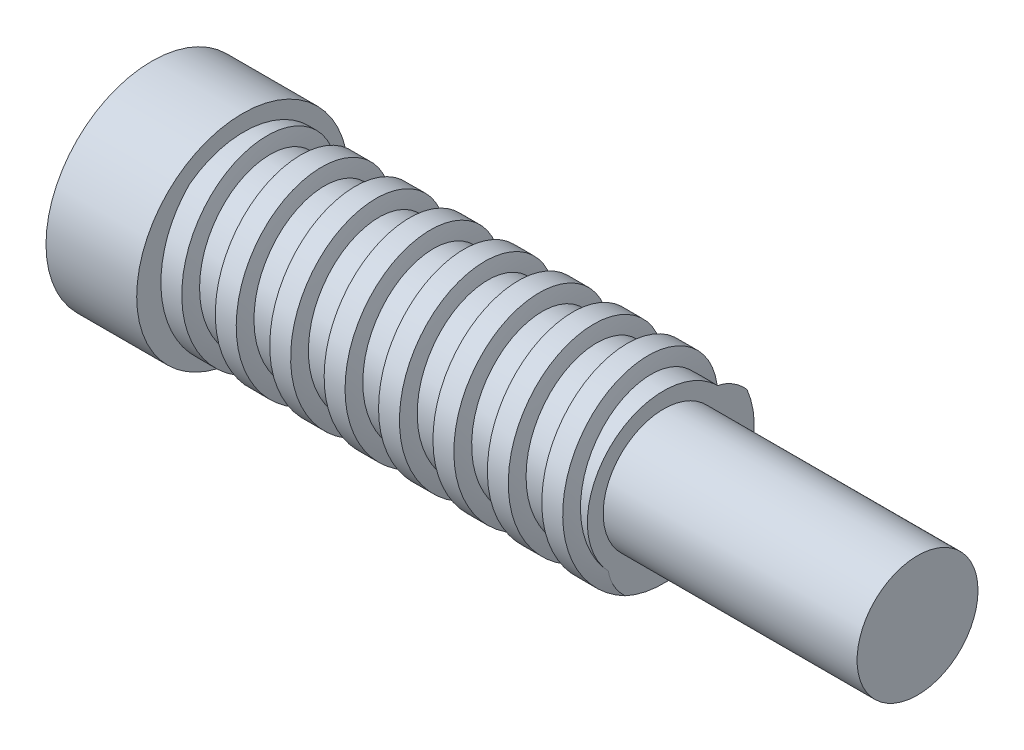
SolidWorks part; units mm, degrees
ref_plane "Piano frontale" through (0, 0, 0) normal (0, 0, 1) x (1, 0, 0)
ref_plane "Piano superiore" through (0, 0, 0) normal (0, 1, 0) x (1, 0, 0)
ref_plane "Piano destro" through (0, 0, 0) normal (1, 0, 0) x (0, 0, -1)
sketch "Schizzo1" plane through (0, 0, 0) normal (0, 0, 1) x (1, 0, 0)
  line L1 (3.0478, 1.2286) -> (21.0478, 1.2286)
  line L2 (3.0478, 1.2286) -> (3.0478, 4.2286)
  line L3 (3.0478, 4.2286) -> (21.0478, 4.2286)
  line L4 (21.0478, 1.2286) -> (21.0478, 4.2286)
  dimension "D1" = 18
  dimension "D2" = 3
revolve "Rivoluzione1" add sketch "Schizzo1" angle 360 about L1
sketch "Schizzo2" plane through (0, 0, 0) normal (0, 0, 1) x (1, 0, 0)
  line L0 (-3.0902, -11.7478) -> (-3.0902, 4.2522) construction
  line L1 (-2.5318, 4.2425) -> (1.2761, 3.1245) construction
  line L2 (-4.1212, 5.2754) -> (-2.0591, 5.2754)
  line L3 (-3.0902, -11.7478) -> (-2.5318, 4.2425) construction
  arc A2 (-2.6436, 3.7458) -> (-3.5368, 3.7458) centre (-3.0902, -11.7478) ccw
  arc A3 (-2.0591, 5.2754) -> (-2.6436, 3.7458) centre (1.2761, 3.1245) ccw
  arc A6 (-4.1212, 5.2754) -> (-3.5368, 3.7458) centre (-7.4565, 3.1245) cw
  point P1 (0, 0)
  dimension "D1" = 31
  dimension "D4" = 2
ref_plane "Piano1" through (24.0478, 0, 0) normal (1, 0, 0) x (0, 0, -1)
sketch "Schizzo3" plane through (24.0478, 0, 0) normal (1, 0, 0) x (0, 0, -1)
  circle A0 centre (0, 1.2286) radius 3 construction
  circle A1 centre (0, 1.2286) radius 3
curve "Elica/Spirale1" pitch 1.8 height 36 radius 3 centre (24.0478, 1.2286, 0) axis (-1, 0, 0) start towards (0, 0, 1)
sweep "Taglia-Sweep2" cut profiles "Schizzo2" path "Elica/Spirale1" align with end faces yes
sketch "Schizzo4" plane through (0, 0, 0) normal (0, 0, 1) x (1, 0, 0)
  line L0 (16.9301, 6.4536) -> (16.9301, -3.1913)
  line L1 (16.9301, -3.1913) -> (25.1287, -3.1913)
  line L2 (25.1287, -3.1913) -> (25.1287, 6.4536)
  line L3 (25.1287, 6.4536) -> (16.9301, 6.4536)
extrude "Taglio-Estrusione1" cut sketch "Schizzo4" along normal through all both and the other way through all
sketch "Schizzo5" plane through (0, 0, 0) normal (1, 0, 0) x (0, 0, -1)
  circle A0 centre (0, 1.2286) radius 3.5
  dimension "D1" = 7
extrude "Estrusione-Estrusione1" add sketch "Schizzo5" along normal blind 3 separate body
sketch "Schizzo6" plane through (0, 0, 0) normal (-1, 0, 0) x (0, 0, 1)
  line L1 (0, 2.7286) -> (-1.299, 1.9786)
  line L2 (-1.299, 1.9786) -> (-1.299, 0.4786)
  line L3 (-1.299, 0.4786) -> (0, -0.2714)
  line L4 (0, -0.2714) -> (1.299, 0.4786)
  line L5 (1.299, 0.4786) -> (1.299, 1.9786)
  line L6 (1.299, 1.9786) -> (0, 2.7286)
  circle A0 centre (0, 1.2286) radius 1.299 construction
  dimension "D1" = 1.5
extrude "Taglio-Estrusione2" cut sketch "Schizzo6" against normal blind 5
sketch "Schizzo7" plane through (16.9301, 0, 0) normal (1, 0, 0) x (0, 0, -1)
  circle A0 centre (0, 1.2286) radius 2
  dimension "D1" = 4
extrude "Estrusione-Estrusione2" add sketch "Schizzo7" along normal blind 8.4
